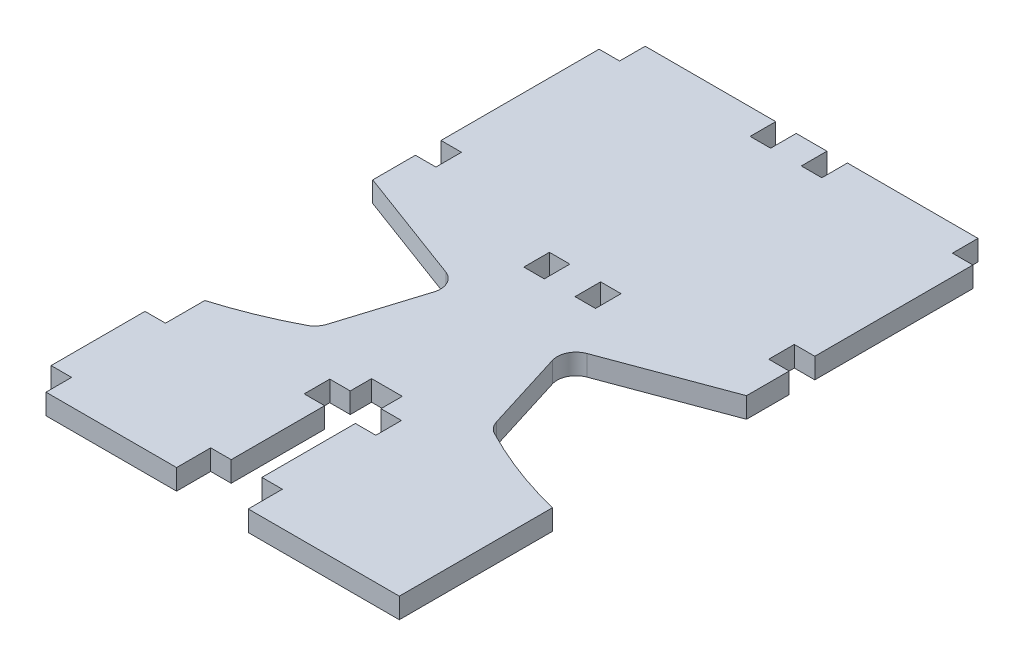
SolidWorks part; units mm, degrees
ref_plane "Front" through (0, 0, 0) normal (0, 0, 1) x (1, 0, 0)
ref_plane "Top" through (0, 0, 0) normal (0, 1, 0) x (1, 0, 0)
ref_plane "Right" through (0, 0, 0) normal (1, 0, 0) x (0, 0, -1)
ref_axis "side-side" through (80.9, 0, 0) along (-1, 0, 0)
ref_axis "up-down" through (0, 50, 0) along (0, -1, 0)
ref_axis "front-back" through (0, 0, -80.9) along (0, 0, 1)
sketch "Sketch1" plane through (0, 0, 0) normal (0, 1, 0) x (1, 0, 0)
  line L0 (0, 45.72) -> (0, 82.7528) construction
  line L1 (-49.53, 45.72) -> (-10.668, 45.72)
  line L2 (-55.626, 38.1) -> (-55.626, -8.9519)
  line L3 (-49.53, -132.6173) -> (-10.668, -132.6173)
  line L4 (55.626, 38.1) -> (55.626, -8.9519)
  line L5 (0, -50) -> (0, 50) construction
  line L6 (10.668, -132.6173) -> (55.626, -132.6173)
  line L7 (4.572, -122.4573) -> (10.668, -122.4573)
  line L8 (-17.632, -49.0369) -> (-25.1877, -73.287)
  line L9 (-21.0198, -42.1368) -> (-55.626, -29.2719)
  line L10 (-55.626, -97.0573) -> (-55.626, -124.9973)
  line L11 (55.626, -29.2719) -> (21.0198, -42.1368)
  line L12 (17.632, -49.0369) -> (25.1877, -73.287)
  line L13 (55.626, -87.0224) -> (55.626, -132.6173)
  line L14 (55.626, -16.5719) -> (55.626, -29.2719)
  line L15 (-49.53, 38.1) -> (-55.626, 38.1)
  line L16 (-49.53, 38.1) -> (-49.53, 45.72)
  line L17 (-55.626, -16.5719) -> (-55.626, -29.2719)
  line L19 (-49.53, -8.9519) -> (-55.626, -8.9519)
  line L20 (-49.53, -8.9519) -> (-49.53, -16.5719)
  line L21 (-49.53, -16.5719) -> (-55.626, -16.5719)
  line L23 (-57.4537, -89.4373) -> (-47.6065, -89.4373) construction
  line L24 (-4.572, -113.8762) -> (-4.572, -154.2073) construction
  line L25 (55.626, 38.1) -> (49.53, 38.1)
  line L26 (49.53, 45.72) -> (49.53, 38.1)
  line L27 (55.626, -16.5719) -> (49.53, -16.5719)
  line L28 (4.572, -113.8762) -> (4.572, -154.2073) construction
  line L29 (55.626, -8.9519) -> (49.53, -8.9519)
  line L30 (49.53, -16.5719) -> (49.53, -8.9519)
  line L31 (-55.626, -124.9973) -> (-49.53, -124.9973)
  line L32 (-49.53, -132.6173) -> (-49.53, -124.9973)
  line L33 (-4.572, -94.6424) -> (-4.572, -122.4573)
  line L34 (4.572, -94.6424) -> (4.572, -122.4573)
  line L35 (-10.668, -94.6424) -> (-10.668, -87.0224) construction
  line L36 (4.572, -94.6424) -> (10.668, -94.6424)
  line L37 (-10.668, -87.0224) -> (-4.572, -87.0224)
  line L38 (-10.668, -87.0224) -> (-10.668, -94.6424)
  line L39 (-55.626, -97.0573) -> (-49.53, -97.0573)
  line L40 (-49.53, -85.3598) -> (-49.53, -97.0573)
  line L41 (-10.668, -94.6424) -> (-4.572, -94.6424)
  line L42 (10.668, -87.0224) -> (10.668, -94.6424)
  line L43 (10.668, 45.72) -> (49.53, 45.72)
  line L44 (-10.668, -132.6173) -> (-10.668, -122.4573)
  line L45 (-10.668, -122.4573) -> (-4.572, -122.4573)
  line L46 (10.668, -132.6173) -> (10.668, -122.4573)
  line L47 (-4.572, 45.72) -> (4.572, 45.72)
  line L48 (-10.668, 45.72) -> (-10.668, 38.1)
  line L49 (-10.668, 38.1) -> (-4.572, 38.1)
  line L50 (-4.572, 45.72) -> (-4.572, 38.1)
  line L51 (-4.572, 20.2034) -> (-4.572, -113.8762) construction
  line L52 (4.572, 45.72) -> (4.572, 38.1)
  line L53 (4.572, 38.1) -> (10.668, 38.1)
  line L54 (10.668, 45.72) -> (10.668, 38.1)
  line L55 (10.668, -21.6519) -> (4.572, -21.6519)
  line L56 (10.668, -21.6519) -> (10.668, -29.2719)
  line L57 (10.668, -29.2719) -> (4.572, -29.2719)
  line L58 (4.572, -21.6519) -> (4.572, -29.2719)
  line L59 (-10.668, -21.6519) -> (-4.572, -21.6519)
  line L60 (-10.668, -21.6519) -> (-10.668, -29.2719)
  line L61 (-10.668, -29.2719) -> (-4.572, -29.2719)
  line L62 (-4.572, -21.6519) -> (-4.572, -29.2719)
  line L63 (-55.626, -8.9519) -> (-55.626, 38.1) construction
  line L64 (-4.572, -87.0224) -> (-4.572, -80.6724)
  line L65 (-4.572, -80.6724) -> (4.572, -80.6724)
  line L66 (4.572, -87.0224) -> (4.572, -80.6724)
  line L67 (4.572, 20.2034) -> (4.572, -113.8762) construction
  line L68 (4.572, -87.0224) -> (10.668, -87.0224)
  line L69 (-49.53, -8.9519) -> (-49.53, 38.1) construction
  arc A1 (-17.632, -49.0369) -> (-21.0198, -42.1368) centre (-22.967, -47.3746) ccw
  arc A2 (-27.9391, -76.5796) -> (-25.1877, -73.287) centre (-30.5228, -71.6248) ccw
  arc A3 (-27.9391, -76.5796) -> (-49.53, -85.3598) centre (-85.09, 33.02) cw
  arc A4 (21.0198, -42.1368) -> (17.632, -49.0369) centre (22.967, -47.3746) ccw
  arc A5 (25.1877, -73.287) -> (27.9391, -76.5796) centre (30.5228, -71.6248) ccw
  arc A6 (27.9391, -76.5796) -> (55.626, -87.0224) centre (85.09, 33.02) ccw
  dimension "D2" = 11.176
  dimension "D1" = 15.24
  dimension "D3" = 12.7
  dimension "D4" = 7.62
  dimension "D5" = 35.56
  dimension "D6" = 6.35
  dimension "D7" = 7.62
extrude "Boss-Extrude1" add sketch "Sketch1" along normal mid plane 6.096
